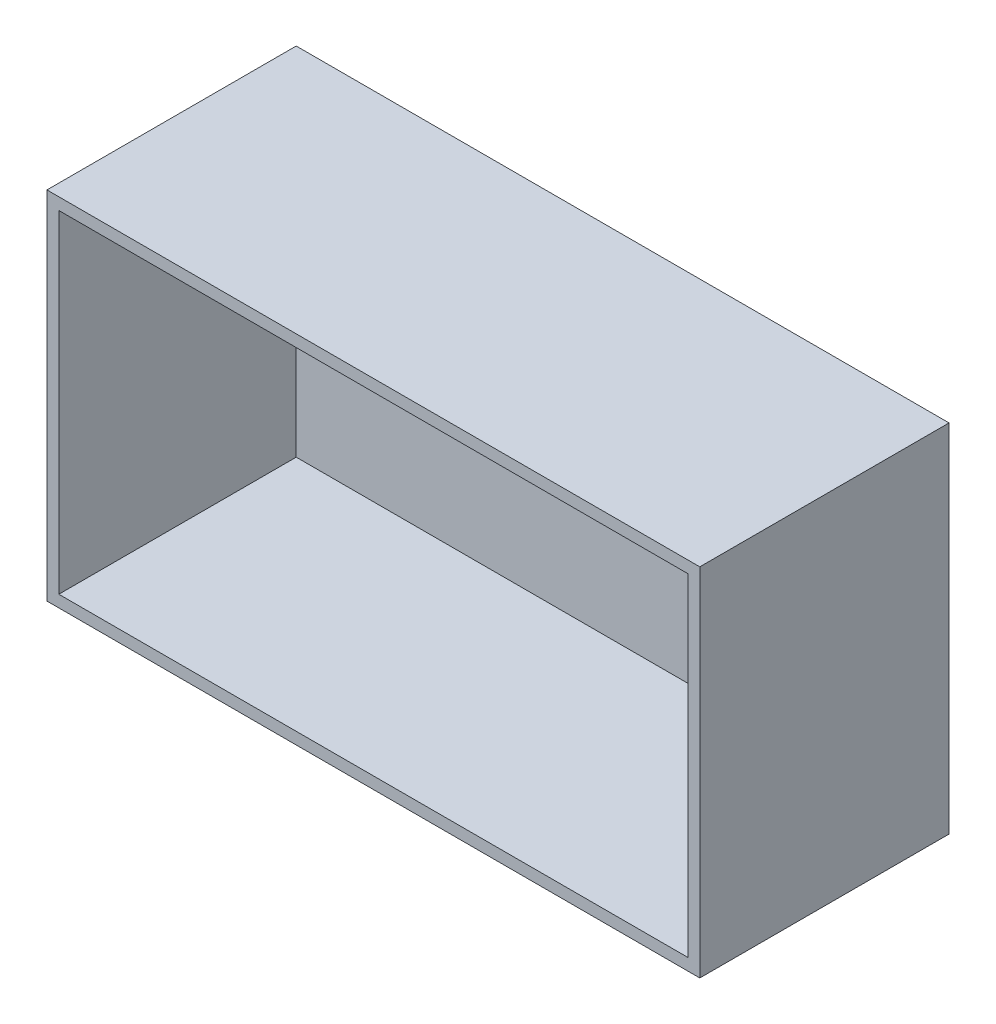
SolidWorks part; units mm, degrees
ref_plane "前视基准面" through (0, 0, 0) normal (0, 0, 1) x (1, 0, 0)
ref_plane "上视基准面" through (0, 0, 0) normal (0, 1, 0) x (1, 0, 0)
ref_plane "右视基准面" through (0, 0, 0) normal (1, 0, 0) x (0, 0, -1)
sketch "草图1" plane through (0, 0, 0) normal (0, 0, 1) x (1, 0, 0)
  line L1 (0, 0) -> (110, 0)
  line L2 (0, 0) -> (0, 60)
  line L3 (0, 60) -> (110, 60)
  line L4 (110, 0) -> (110, 60)
  dimension "D1" = 60
  dimension "D2" = 110
extrude "凸台-拉伸1" add sketch "草图1" along normal blind 2
sketch "草图2" plane through (0, 0, 2) normal (0, 0, 1) x (1, 0, 0)
  line L4 (108, 58) -> (2, 58)
  line L5 (2, 58) -> (2, 2)
  line L6 (2, 2) -> (108, 2)
  line L7 (108, 2) -> (108, 58)
  line L8 (0, 60) -> (0, 0)
  line L9 (0, 0) -> (110, 0)
  line L10 (110, 0) -> (110, 60)
  line L11 (110, 60) -> (0, 60)
  line L12 (0, 60) -> (0, 0)
  line L13 (0, 0) -> (110, 0)
  line L14 (110, 0) -> (110, 60)
  line L15 (110, 60) -> (0, 60)
  dimension "D1" = 0
  dimension "D2" = 2
extrude "凸台-拉伸2" add sketch "草图2" along normal blind 40
